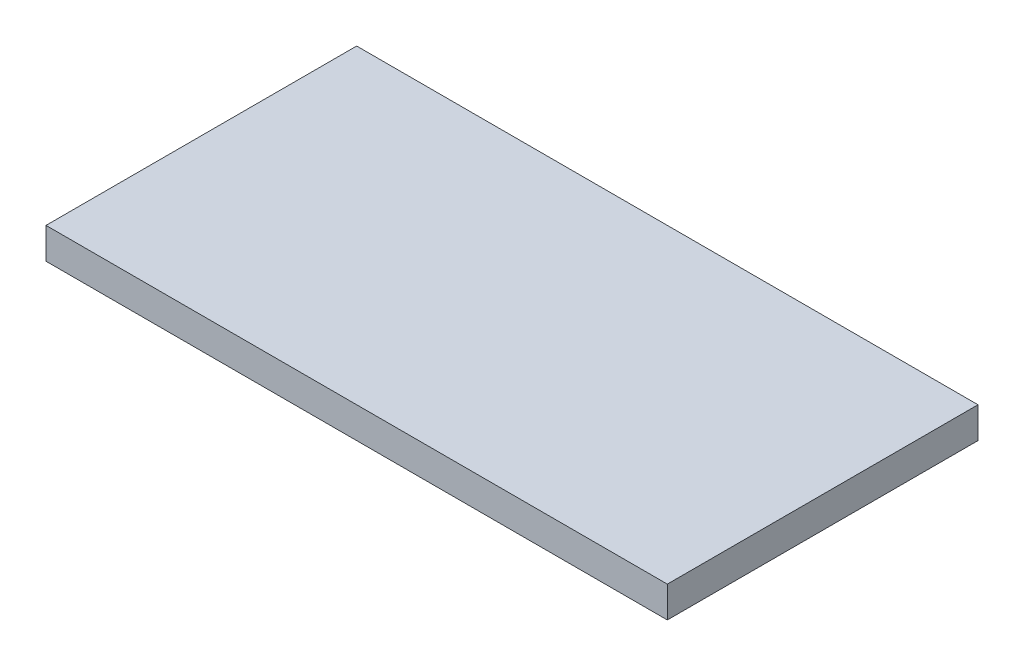
SolidWorks part; units mm, degrees
ref_plane "Front Plane" through (0, 0, 0) normal (0, 0, 1) x (1, 0, 0)
ref_plane "Top Plane" through (0, 0, 0) normal (0, 1, 0) x (1, 0, 0)
ref_plane "Right Plane" through (0, 0, 0) normal (1, 0, 0) x (0, 0, -1)
sketch "Sketch1" plane through (0, 0, 0) normal (0, 1, 0) x (1, 0, 0)
  line L1 (-50.8, -25.4) -> (50.8, -25.4)
  line L2 (-50.8, -25.4) -> (-50.8, 25.4)
  line L3 (-50.8, 25.4) -> (50.8, 25.4)
  line L4 (50.8, -25.4) -> (50.8, 25.4)
  line L5 (-50.8, -25.4) -> (50.8, 25.4) construction
  line L6 (-50.8, 25.4) -> (50.8, -25.4) construction
  point P0 (0, 0)
  dimension "D1" = 101.6
  dimension "D2" = 50.8
base flange "Base-Flange1" sketch "Sketch1" thickness 5.08 reverse thickness direction no parameters "D1"=0.7366
sketch "Bend-Lines1" [suppressed] plane through (0, 0, 0) normal (0, 1, 0) x (1, 0, 0)
sketch "Bounding-Box1" [suppressed] plane through (0, 0, 0) normal (0, 1, 0) x (1, 0, 0)
sheet metal parameters "Sheet-Metal1" thickness 5.08 parameters "D1"=0.7366
flat pattern "Flat-Pattern1" [suppressed]
sketch "Bend-Lines2" plane through (0, 0, 0) normal (0, 1, 0) x (1, 0, 0)
sketch3d "Bounding-Box2" [suppressed]
  line L0 (-50.8, 25.4, 0) -> (50.8, 25.4, 0) construction
  line L1 (-50.8, -25.4, 0) -> (50.8, -25.4, 0) construction
  line L2 (-50.8, 25.4, 0) -> (-50.8, -25.4, 0) construction
  line L3 (50.8, 25.4, 0) -> (50.8, -25.4, 0) construction
